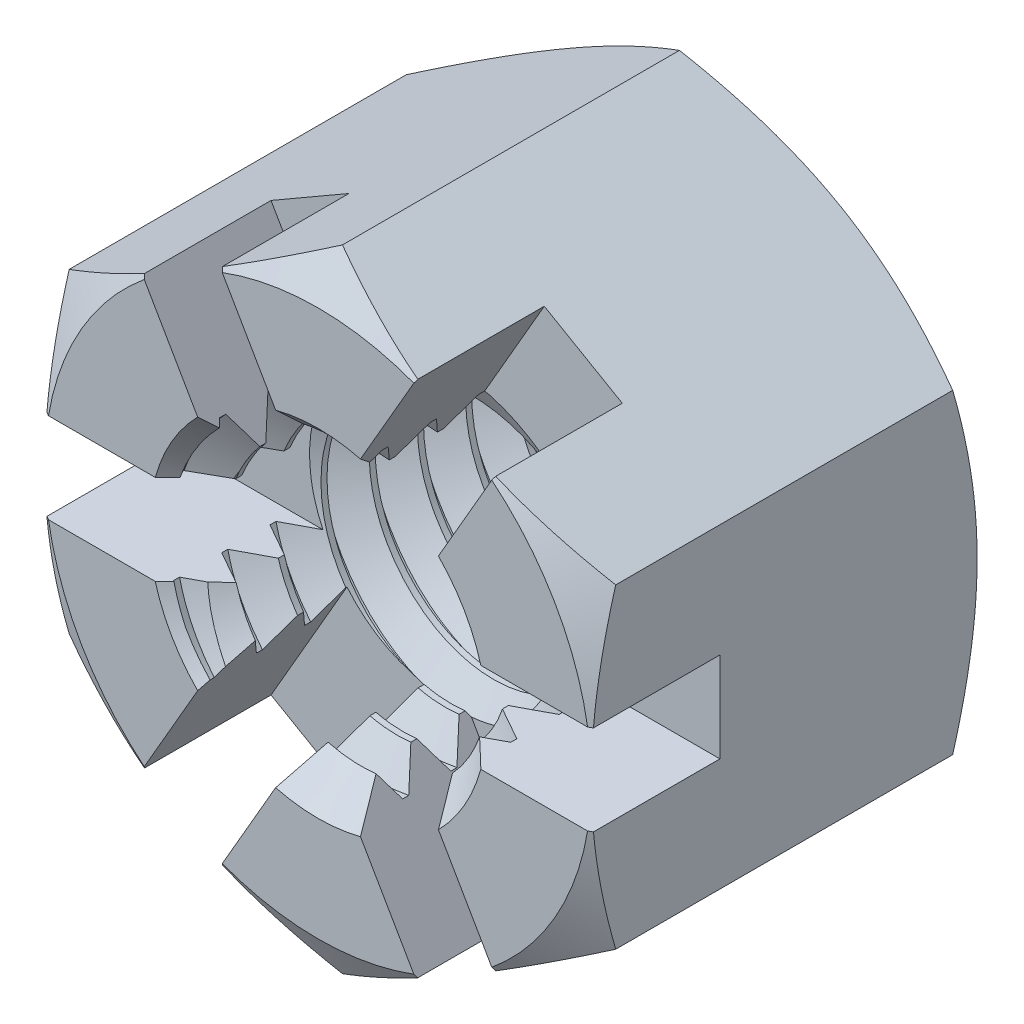
SolidWorks part; units mm, degrees
ref_plane "Front Plane" through (0, 0, 0) normal (0, 0, 1) x (1, 0, 0)
ref_plane "Top Plane" through (0, 0, 0) normal (0, 1, 0) x (1, 0, 0)
ref_plane "Right Plane" through (0, 0, 0) normal (1, 0, 0) x (0, 0, -1)
sketch "Sketch1" plane through (0, 0, 0) normal (0, 0, 1) x (1, 0, 0)
  line L1 (0, 9.815) -> (-8.5, 4.9075)
  line L2 (-8.5, 4.9075) -> (-8.5, -4.9075)
  line L3 (-8.5, -4.9075) -> (0, -9.815)
  line L4 (0, -9.815) -> (8.5, -4.9075)
  line L5 (8.5, -4.9075) -> (8.5, 4.9075)
  line L6 (8.5, 4.9075) -> (0, 9.815)
  circle A0 centre (0, 0) radius 8.5 construction
  dimension "Hex" = 17
extrude "Extrude1" add sketch "Sketch1" against normal blind 12
sketch "Sketch2" plane through (0, 0, 0) normal (0, 0, 1) x (1, 0, 0)
  circle A0 centre (0, 0) radius 8.5 construction
  circle A1 centre (0, 0) radius 8.5
sketch "Sketch3" plane through (0, 0, -12) normal (0, 0, -1) x (-1, 0, 0)
  circle A1 centre (0, 0) radius 8.5
  circle A2 centre (0, 0) radius 8.5
  dimension "D1" = 0
extrude "Cut-Extrude2" cut sketch "Sketch3" against normal through all draft 60 flip side to cut
sketch "Sketch4" plane through (0, 0, 0) normal (0, 0, 1) x (1, 0, 0)
  circle A0 centre (0, 0) radius 5
  dimension "Thread Dia" = 10
extrude "Cut-Extrude3" cut sketch "Sketch4" against normal through all
sketch "Sketch7" plane through (0, 0, 0) normal (0, 0, 1) x (1, 0, 0)
  circle A4 centre (0, 0) radius 5.254
  circle A5 centre (0, 0) radius 5.254
  dimension "D1" = 0.254
sketch "Sketch8" plane through (0, 0, -12) normal (0, 0, -1) x (-1, 0, 0)
  circle A1 centre (0, 0) radius 5.254
  circle A2 centre (0, 0) radius 5.254 construction
sketch "Sketch5" plane through (0, 0, 0) normal (0, 0, 1) x (1, 0, 0)
  circle A0 centre (0, 0) radius 5 construction
  circle A1 centre (0, 0) radius 5
curve "Helix/Spiral1" pitch 1.5 height 13.5 turns 9 parameters "pitch"=1.5
sketch "Sketch9" plane through (0, 0, 0) normal (1, 0, 0) x (0, 0, -1)
  line L0 (-0.75, 5) -> (-0.5625, 5)
  line L1 (-0.5625, 5) -> (0, 4.0257)
  line L2 (-0.75, 5) -> (-1.3125, 4.0257)
  line L3 (-1.3125, 4.0257) -> (0, 4.0257)
  line L4 (-0.6562, 5) -> (-0.6562, 4.0257) construction
  line L5 (-1.0312, 4.5129) -> (-0.2812, 4.5129) construction
  line L7 (0, 4.0257) -> (0, 5) construction
  line L8 (0, 5) -> (0, -5) construction
  dimension "D1" = 0.1875
  dimension "D2" = 0.75
  dimension "D3" = 60
sketch "Sketch12" plane through (0, 0, 0) normal (0, 0, 1) x (1, 0, 0)
  circle A0 centre (0, 0) radius 4.0257
  circle A1 centre (0, 0) radius 5 construction
  circle A2 centre (0, 0) radius 5
extrude "Extrude2" add sketch "Sketch12" against normal up to surface (12 mm away) up to face at (5, 0, -12)
sweep "Cut-Sweep1" cut profiles "Sketch9" path "Helix/Spiral1"
extrude "Cut-Extrude6" cut sketch "Sketch7" against normal through all draft 45
extrude "Cut-Extrude7" cut sketch "Sketch8" against normal through all draft 45
sketch "Sketch16" plane through (0, 0, 0) normal (0, 0, 1) x (1, 0, 0)
  circle A0 centre (0, 0) radius 8.5 construction
  circle A1 centre (0, 0) radius 8.5
extrude "Cut-Extrude11" cut sketch "Sketch16" against normal through all draft 60 flip side to cut
sketch "Sketch13" plane through (0, 0, 0) normal (0, 0, 1) x (1, 0, 0)
  line L0 (-1.2124, 0.7) -> (1.2124, -0.7)
  line L1 (-1.2124, 0.7) -> (3.0376, 8.0612)
  line L2 (1.2124, -0.7) -> (5.4624, 6.6612)
  line L3 (3.0376, 8.0612) -> (5.4624, 6.6612)
  line L5 (8.5, 4.9075) -> (0, 9.815) construction
  dimension "slot width" = 2.8
extrude "Cut-Extrude8" cut sketch "Sketch13" against normal blind 4
sketch "Sketch14" [suppressed] plane through (0, 0, -8) normal (0, 0, 1) x (1, 0, 0)
  circle A0 centre (0, 0) radius 18 construction
  circle A1 centre (0, 0) radius 18
extrude "Cut-Extrude9" [suppressed] cut sketch "Sketch14" against normal through all draft 60 flip side to cut
sketch "Sketch15" [suppressed] plane through (0, 0, 0) normal (0, 0, 1) x (1, 0, 0)
  circle A0 centre (0, 0) radius 18 construction
  circle A1 centre (0, 0) radius 18
extrude "Cut-Extrude10" [suppressed] cut sketch "Sketch15" against normal up to surface (8 mm away) flip side to cut
pattern_circular "CirPattern1" count 6 over 360 about axis through (0, 0, 0) along (0, 0, 1) of "Cut-Extrude8"
equation "\"D2@Sketch9\" = \"pitch@Helix/Spiral1\"*.5"
equation "\"D3@Helix/Spiral1\" = \"pitch@Helix/Spiral1\"+\"Height@Extrude1\""
equation "\"D1@Sketch9\" = \"pitch@Helix/Spiral1\"*.125"
